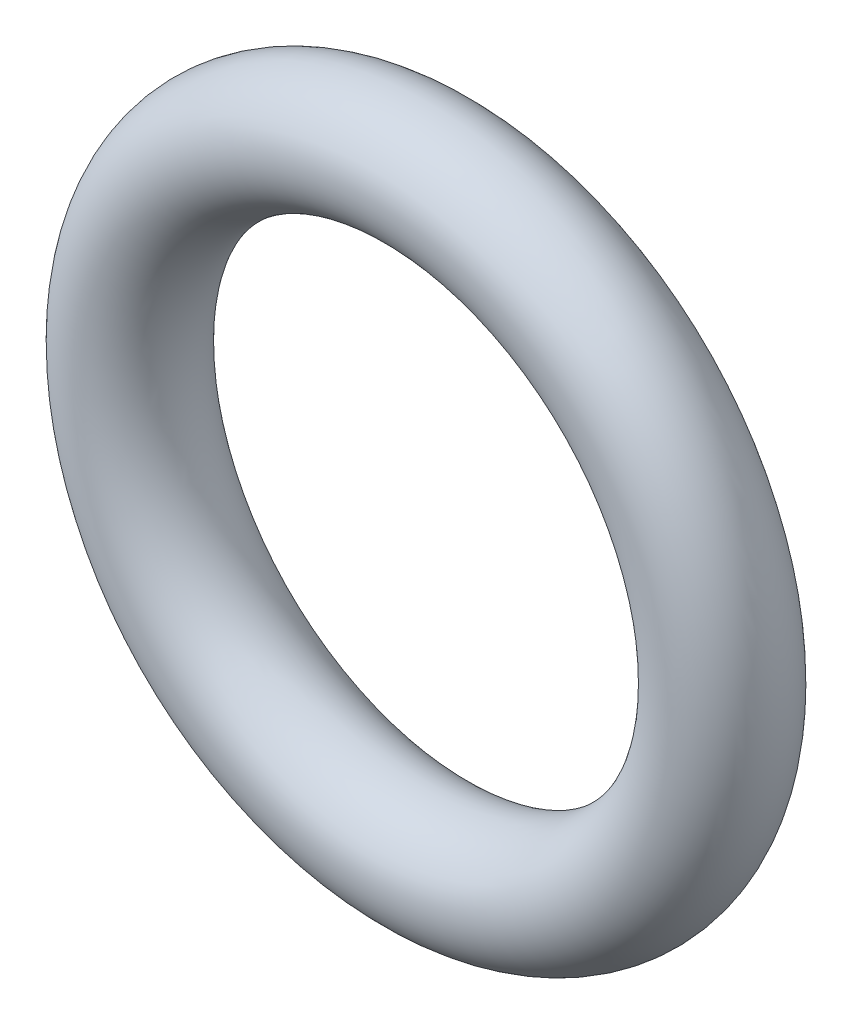
SolidWorks part; units mm, degrees
ref_plane "Front Plane" through (0, 0, 0) normal (0, 0, 1) x (1, 0, 0)
ref_plane "Top Plane" through (0, 0, 0) normal (0, 1, 0) x (1, 0, 0)
ref_plane "Right Plane" through (0, 0, 0) normal (1, 0, 0) x (0, 0, -1)
ref_axis "Axis1" through (0, 0, -88.99) along (0, 0, 1)
sketch "Sketch1" plane through (0, 0, 0) normal (0, 1, 0) x (1, 0, 0)
  line L0 (-0.4976, 0) -> (0.4976, 0) construction
  line L1 (0, -0.4976) -> (0, 0.4976) construction
  circle A0 centre (-1.25, 0) radius 0.25
  point P4 (0, 0)
  dimension "D1" = 0.5
  dimension "D2" = 1.25
revolve "Revolve1" add sketch "Sketch1" angle 360 about axis through (0, 0, -88.99) along (0, 0, 1)
